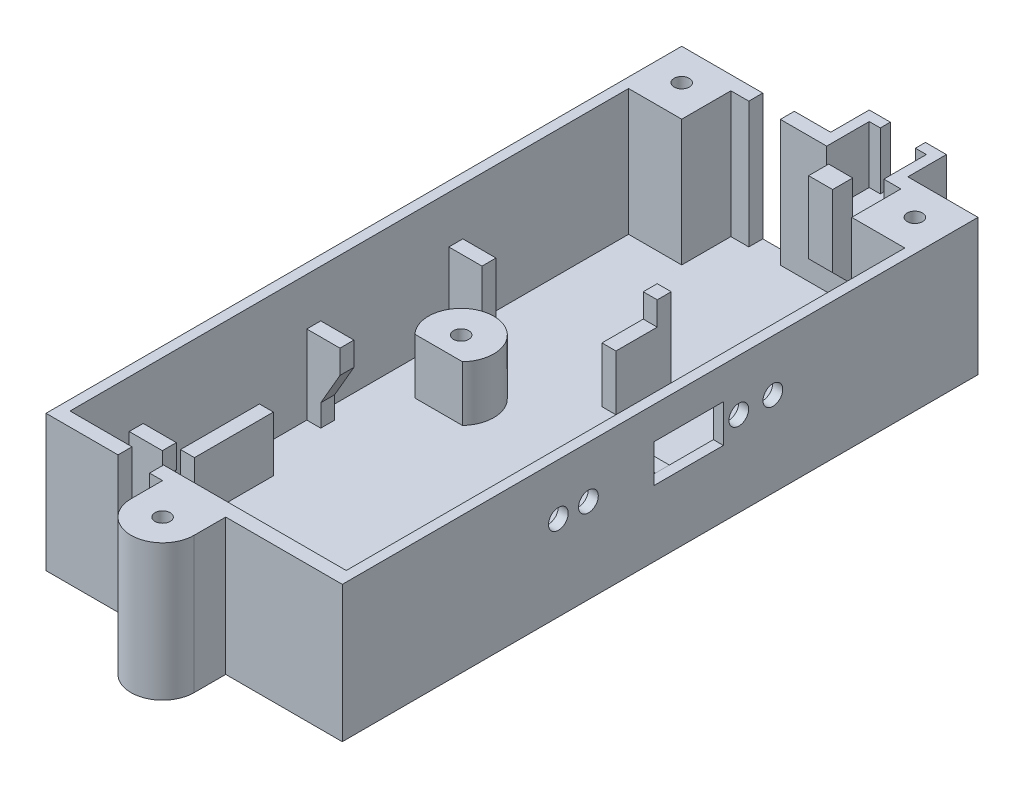
SolidWorks part; units mm, degrees
ref_plane "Front Plane" through (0, 0, 0) normal (0, 0, 1) x (1, 0, 0)
ref_plane "Top Plane" through (0, 0, 0) normal (0, 1, 0) x (1, 0, 0)
ref_plane "Right Plane" through (0, 0, 0) normal (1, 0, 0) x (0, 0, -1)
sketch "Sketch2" plane through (0, 0, 0) normal (0, 0, 1) x (1, 0, 0)
  line L0 (-30.2154, 3.088) -> (-30.2154, -12.912)
  line L1 (-30.2154, -12.912) -> (4.7846, -12.912)
  line L2 (4.7846, -12.912) -> (4.7846, 3.088)
  line L3 (-31.4854, 3.088) -> (-31.4854, -14.182)
  line L4 (-31.4854, -14.182) -> (6.0546, -14.182)
  line L5 (6.0546, -14.182) -> (6.0546, 3.088)
  line L6 (-31.4854, 3.088) -> (-30.2154, 3.088)
  line L7 (4.7846, 3.088) -> (6.0546, 3.088)
  dimension "D1" = 16
  dimension "D2" = 16
  dimension "D3" = 35
  dimension "D4" = 1.27
extrude "Boss-Extrude1" add sketch "Sketch2" along normal blind 77
sketch "Sketch3" plane through (0, 0, 77) normal (0, 0, 1) x (1, 0, 0)
  line L1 (-31.4854, 3.088) -> (6.0546, 3.088)
  line L2 (-31.4854, 3.088) -> (-31.4854, -14.182)
  line L3 (-31.4854, -14.182) -> (6.0546, -14.182)
  line L4 (6.0546, 3.088) -> (6.0546, -14.182)
extrude "Boss-Extrude2" add sketch "Sketch3" along normal blind 1.77
sketch "Sketch4" plane through (0, 0, 0) normal (0, 0, -1) x (-1, 0, 0)
  line L1 (-6.0546, 3.088) -> (31.4854, 3.088)
  line L2 (-6.0546, 3.088) -> (-6.0546, -14.182)
  line L3 (-6.0546, -14.182) -> (31.4854, -14.182)
  line L4 (31.4854, 3.088) -> (31.4854, -14.182)
extrude "Boss-Extrude3" add sketch "Sketch4" along normal blind 1.77
sketch "Sketch5" plane through (0, 0, -1.77) normal (0, 0, -1) x (-1, 0, 0)
  line L0 (31.4854, 3.088) -> (-6.0546, 3.088) construction
  line L1 (17.2154, 3.088) -> (21.2154, 3.088)
  line L2 (17.2154, 3.088) -> (17.2154, -12.912)
  line L3 (17.2154, -12.912) -> (21.2154, -12.912)
  line L4 (21.2154, 3.088) -> (21.2154, -12.912)
  line L5 (-4.7846, -12.912) -> (30.2154, -12.912) construction
  line L6 (30.2154, -12.912) -> (30.2154, 3.088) construction
  dimension "D1" = 4
  dimension "D2" = 9
extrude "Cut-Extrude2" cut sketch "Sketch5" against normal blind 1.77
sketch "Sketch6" plane through (0, 3.088, 0) normal (0, 1, 0) x (1, 0, 0)
  line L0 (4.7846, -77) -> (4.7846, 0) construction
  line L1 (-11.3454, 5.39) -> (-4.1054, 5.39)
  line L2 (-11.3454, 5.39) -> (-11.3454, -1.85)
  line L3 (-11.3454, -1.85) -> (-4.1054, -1.85)
  line L4 (-4.1054, 5.39) -> (-4.1054, -1.85)
  line L5 (-12.6154, 6.66) -> (-2.8354, 6.66)
  line L6 (-12.6154, 6.66) -> (-12.6154, -4.39)
  line L7 (-12.6154, -4.39) -> (-2.8354, -4.39)
  line L8 (-2.8354, 6.66) -> (-2.8354, -4.39)
  line L9 (-17.2154, 1.77) -> (6.0546, 1.77) construction
  dimension "D1" = 1.27
  dimension "D2" = 1.27
  dimension "D3" = 8.89
  dimension "D4" = 7.24
  dimension "D5" = 1.27
  dimension "D6" = 2.54
  dimension "D7" = 7.24
  dimension "D8" = 3.62
extrude "button_walls" add sketch "Sketch6" against normal blind 7.24
sketch "Sketch7" plane through (0, -4.152, 0) normal (0, -1, 0) x (1, 0, 0)
  line L1 (-12.6154, 4.39) -> (-2.8354, 4.39)
  line L2 (-12.6154, 4.39) -> (-12.6154, -6.66)
  line L3 (-12.6154, -6.66) -> (-2.8354, -6.66)
  line L4 (-2.8354, 4.39) -> (-2.8354, -6.66)
extrude "button_bottom" add sketch "Sketch7" along normal blind 1.27
sketch "Sketch8" plane through (0, 3.088, 0) normal (0, 1, 0) x (1, 0, 0)
  line L0 (-11.3454, 0) -> (-4.1054, 0) construction
  line L1 (-11.3454, 1.77) -> (-4.1054, 1.77)
  line L2 (-11.3454, 1.77) -> (-11.3454, 0)
  line L3 (-11.3454, 0) -> (-4.1054, 0)
  line L4 (-4.1054, 1.77) -> (-4.1054, 0)
extrude "button_cutout_middle" cut sketch "Sketch8" against normal blind 7.24
sketch "Sketch9" plane through (0, 3.088, 0) normal (0, 1, 0) x (1, 0, 0)
  line L0 (-7.7254, 9.378) -> (-7.7254, -7.9569) construction
  line L1 (-2.8354, 6.66) -> (-12.6154, 6.66) construction
  line L2 (-9.9454, 6.66) -> (-5.4954, 6.66)
  line L3 (-9.9454, 6.66) -> (-9.9454, 5.39)
  line L4 (-9.9454, 5.39) -> (-5.4954, 5.39)
  line L5 (-5.4954, 6.66) -> (-5.4954, 5.39)
  line L6 (-4.1054, 5.39) -> (-11.3454, 5.39) construction
  line L13 (-12.6154, -4.39) -> (-2.8354, -4.39) construction
  line L14 (-12.6154, 0) -> (-9.2454, 0)
  line L15 (-12.6154, 0) -> (-12.6154, -4.39)
  line L16 (-12.6154, -4.39) -> (-9.2454, -4.39)
  line L17 (-9.2454, 0) -> (-9.2454, -4.39)
  line L19 (-2.8354, 0) -> (-6.2054, 0)
  line L20 (-2.8354, 0) -> (-2.8354, -4.39)
  line L21 (-2.8354, -4.39) -> (-6.2054, -4.39)
  line L22 (-6.2054, 0) -> (-6.2054, -4.39)
  dimension "D1" = 4.45
  dimension "D2" = 2.22
  dimension "D3" = 1.52
  dimension "D4" = 1.52
extrude "button_cutout_front_back" cut sketch "Sketch9" against normal blind 7.24
sketch "Sketch10" plane through (0, -4.152, 0) normal (0, 1, 0) x (1, 0, 0)
  line L1 (-12.6154, 0) -> (-9.2454, 0)
  line L2 (-12.6154, 0) -> (-12.6154, -4.39)
  line L3 (-12.6154, -4.39) -> (-9.2454, -4.39)
  line L4 (-9.2454, 0) -> (-9.2454, -4.39)
  line L5 (-2.8354, 0) -> (-6.2054, 0)
  line L6 (-2.8354, 0) -> (-2.8354, -4.39)
  line L7 (-2.8354, -4.39) -> (-6.2054, -4.39)
  line L8 (-6.2054, 0) -> (-6.2054, -4.39)
extrude "button_cutout_bottom" cut sketch "Sketch10" against normal blind 1.27
chamfer "button_Chamfer1" distance 5 angle 45 1 edges at (-7.7254, -5.422, 0)
sketch "Sketch12" plane through (0, -12.912, 0) normal (0, 1, 0) x (1, 0, 0)
  line L0 (4.7846, -77) -> (-30.2154, -77) construction
  line L1 (-30.2154, -77) -> (4.7846, -77)
  line L2 (-30.2154, -77) -> (-30.2154, -75.23)
  line L3 (-30.2154, -75.23) -> (4.7846, -75.23)
  line L4 (4.7846, -77) -> (4.7846, -75.23)
  line L5 (4.7846, -77) -> (4.7846, 0) construction
  line L11 (4.7846, -77) -> (4.7846, 0) construction
  line L12 (-27.9854, -55.23) -> (-26.2154, -55.23)
  line L13 (-27.9854, -55.23) -> (-27.9854, -65.23)
  line L14 (-27.9854, -65.23) -> (-26.2154, -65.23)
  line L15 (-26.2154, -55.23) -> (-26.2154, -65.23)
  line L16 (4.7846, -37.73) -> (-60.4587, -37.73) construction
  line L17 (-2.7154, -35.96) -> (4.7846, -35.96)
  line L18 (-2.7154, -35.96) -> (-2.7154, -37.73)
  line L19 (-2.7154, -37.73) -> (4.7846, -37.73)
  line L20 (4.7846, -35.96) -> (4.7846, -37.73)
  line L21 (-25.7839, -37.73) -> (-19.7648, -37.73)
  line L22 (-54.4351, -21.6) -> (25.4799, -21.6) construction
  line L24 (-12.9854, -19.83) -> (-11.2154, -19.83)
  line L25 (-12.9854, -19.83) -> (-12.9854, -26.83)
  line L26 (-12.9854, -26.83) -> (-11.2154, -26.83)
  line L27 (-11.2154, -19.83) -> (-11.2154, -26.83)
  arc A0 (-19.7648, -37.73) -> (-25.7839, -37.73) centre (-22.7744, -34.8868) ccw
  circle A1 centre (-22.7744, -34.8868) radius 0.9652
  point P29 (-12.1004, -19.83)
  dimension "D11" = 8.2804
  dimension "D12" = 1.9304
  dimension "D1" = 1.77
  dimension "D2" = 31
  dimension "D3" = 1.77
  dimension "D4" = 10
  dimension "D5" = 10
  dimension "D6" = 1.77
  dimension "D7" = 7.5
  dimension "D8" = 37.5
  dimension "D9" = 42.1132
  dimension "D10" = 27.559
  dimension "D13" = 55.4
  dimension "D14" = 1.77
  dimension "D15" = 7
  dimension "D16" = 1.77
  dimension "D17" = 16
extrude "support_pcb_battery" add sketch "Sketch12" along normal blind 7
sketch "Sketch13" plane through (6.0546, 0, 0) normal (1, 0, 0) x (0, 0, -1)
  line L0 (-77, 3.088) -> (-77, -22.3902) construction
  line L1 (-81.5091, -5.912) -> (21.2567, -5.912) construction
  line L3 (-39.2868, -1.012) -> (-30.4868, -1.012)
  line L4 (-39.2868, -1.012) -> (-39.2868, -5.812)
  line L5 (-39.2868, -5.812) -> (-30.4868, -5.812)
  line L6 (-30.4868, -1.012) -> (-30.4868, -5.812)
  circle A0 centre (-51.3968, -3.412) radius 1.25
  circle A1 centre (-47.5868, -3.412) radius 1.25
  circle A2 centre (-24.2188, -3.412) radius 1.25
  point P10 (-30.4868, -3.412)
  point P11 (-34.8868, -1.012)
  dimension "D7" = 2.5
  dimension "D8" = 2.5
  dimension "D11" = 2.5
  dimension "D1" = 8.8
  dimension "D2" = 2.5
  dimension "D3" = 4.8
  dimension "D4" = 42.1132
  dimension "D5" = 2.5
  dimension "D6" = 2.5
  dimension "D9" = 25.6032
  dimension "D10" = 29.4132
  dimension "D12" = 2.5
  dimension "D13" = 52.7812
extrude "cutout_usb_3_leds" cut sketch "Sketch13" against normal blind 1.77
sketch "Sketch16" plane through (0, -5.912, 0) normal (0, 1, 0) x (1, 0, 0)
  line L0 (-11.2154, -26.83) -> (-11.2154, -19.83) construction
  line L1 (-12.9854, -19.83) -> (-11.2154, -19.83)
  line L2 (-12.9854, -19.83) -> (-12.9854, -21.6)
  line L3 (-12.9854, -21.6) -> (-11.2154, -21.6)
  line L4 (-11.2154, -19.83) -> (-11.2154, -21.6)
  dimension "D1" = 1.77
extrude "tab_pcb_retainer_len" add sketch "Sketch16" along normal blind 3
sketch "Sketch17" plane through (0, 3.088, 0) normal (0, 1, 0) x (1, 0, 0)
  line L0 (4.7846, -77) -> (-30.2154, -77) construction
  line L1 (-22.3614, -77) -> (-18.3614, -77)
  line L2 (-22.3614, -77) -> (-22.3614, -78.77)
  line L3 (-22.3614, -78.77) -> (-18.3614, -78.77)
  line L4 (-18.3614, -77) -> (-18.3614, -78.77)
  line L5 (6.0546, -78.77) -> (-31.4854, -78.77) construction
  line L7 (4.7846, -77) -> (4.7846, 0) construction
  point P8 (-20.3614, -77)
  dimension "D1" = 25.146
  dimension "D2" = 4
extrude "cutout_back_mot_wires" cut sketch "Sketch17" against normal up to surface (9 mm away) up to face at (-12.7154, -5.912, 76.115)
sketch "Sketch18" plane through (6.0546, 0, 0) normal (1, 0, 0) x (0, 0, -1)
  line L0 (-77, 3.088) -> (-77, -25.415) construction
  line L1 (-78.77, -5.912) -> (19.6061, -5.912) construction
  circle A0 centre (-28.5368, -3.412) radius 1.25
  dimension "D1" = 2.5
  dimension "D2" = 2.5
  dimension "D3" = 48.4632
extrude "cutout_chg_done_led" cut sketch "Sketch18" against normal blind 10
sketch "Sketch19" plane through (0, -12.912, 0) normal (0, 1, 0) x (1, 0, 0)
  line L0 (-30.2154, -77) -> (38.3127, -77) construction
  line L1 (4.7846, 0) -> (4.7846, -88.7648) construction
  line L2 (-26.0154, 10.814) -> (-26.0154, -88.7648) construction
  line L3 (-30.2154, -77) -> (-30.2154, 0) construction
  line L4 (-30.2154, -67.73) -> (-26.0154, -67.73)
  line L5 (-30.2154, -67.73) -> (-30.2154, -69.5)
  line L6 (-30.2154, -69.5) -> (-26.0154, -69.5)
  line L7 (-26.0154, -67.73) -> (-26.0154, -69.5)
  line L9 (-30.2154, -45.23) -> (-26.0154, -45.23)
  line L10 (-30.2154, -45.23) -> (-30.2154, -47)
  line L11 (-30.2154, -47) -> (-26.0154, -47)
  line L12 (-26.0154, -45.23) -> (-26.0154, -47)
  line L13 (-30.2154, -27.23) -> (-26.0154, -27.23)
  line L14 (-30.2154, -27.23) -> (-30.2154, -29)
  line L15 (-30.2154, -29) -> (-26.0154, -29)
  line L16 (-26.0154, -27.23) -> (-26.0154, -29)
  dimension "D1" = 30.8
  dimension "D2" = 1.77
  dimension "D3" = 7.5
  dimension "D4" = 1.77
  dimension "D5" = 30
  dimension "D6" = 1.77
  dimension "D7" = 48
extrude "tab_pcb_retainers_width" add sketch "Sketch19" along normal blind 10
sketch "Sketch20" plane through (0, 0, 69.5) normal (0, 0, 1) x (1, 0, 0)
  line L0 (-26.0154, -2.912) -> (-33.8352, -2.912) construction
  line L1 (-26.0154, -5.912) -> (-34.7157, -5.912) construction
  line L2 (-30.2154, -5.912) -> (-22.3614, -5.912) construction
  line L3 (-26.0154, -2.912) -> (-26.0154, -12.912) construction
  line L4 (-28.4454, -0.8533) -> (-28.4454, -17.345) construction
  line L5 (-30.2154, -5.912) -> (-30.2154, 3.088) construction
  line L9 (-26.0154, -12.912) -> (-26.0154, -5.912)
  line L15 (-26.0154, -5.912) -> (-28.4454, -10.1209)
  line L16 (-28.4454, -10.1209) -> (-28.4454, -12.912)
  line L17 (-28.4454, -12.912) -> (-26.0154, -12.912)
  dimension "D1" = 1.77
  dimension "D2" = 30
extrude "cutout_retainer_tab_1" cut sketch "Sketch20" against normal blind 1.77
sketch "Sketch21" plane through (0, 0, 47) normal (0, 0, 1) x (1, 0, 0)
  line L0 (-26.0154, -5.912) -> (-28.4454, -10.1209)
  line L1 (-28.4454, -10.1209) -> (-28.4454, -12.912)
  line L2 (-28.4454, -12.912) -> (-26.0154, -12.912)
  line L3 (-26.0154, -12.912) -> (-26.0154, -5.912)
extrude "cutout_retainer_tab_2" cut sketch "Sketch21" against normal blind 1.77
sketch "Sketch23" plane through (0, -14.182, 0) normal (0, -1, 0) x (1, 0, 0)
  line L0 (-12.7154, 88.9305) -> (-12.7154, -20.1968) construction
  line L1 (-37.0904, 86.77) -> (37.2604, 86.77) construction
  line L2 (-31.4854, 78.77) -> (6.0546, 78.77) construction
  line L3 (-37.0904, 82.77) -> (5.1204, 82.77) construction
  line L8 (6.0546, -1.77) -> (-1.9454, -1.77)
  line L9 (6.0546, -1.77) -> (6.0546, 6.23)
  line L10 (6.0546, 6.23) -> (-1.9454, 6.23)
  line L11 (-1.9454, -1.77) -> (-1.9454, 6.23)
  line L12 (-31.4854, -1.77) -> (-23.4854, -1.77)
  line L13 (-31.4854, -1.77) -> (-31.4854, 6.23)
  line L14 (-31.4854, 6.23) -> (-23.4854, 6.23)
  line L15 (-23.4854, -1.77) -> (-23.4854, 6.23)
  line L16 (-8.7154, 86.77) -> (-8.7154, 78.4197) construction
  line L18 (-16.7154, 88.4048) -> (-16.7154, 77.7225) construction
  line L20 (-16.7154, 82.77) -> (-16.7154, 78.77)
  line L21 (-16.7154, 78.77) -> (-8.7154, 78.77)
  line L22 (-8.7154, 78.77) -> (-8.7154, 82.77)
  arc A0 (-16.7154, 82.77) -> (-8.7154, 82.77) centre (-12.7154, 82.77) cw
  circle A2 centre (-27.4854, 2.23) radius 0.9652
  circle A3 centre (2.0546, 2.23) radius 0.9652
  circle A4 centre (-12.7154, 82.77) radius 0.9652
  point P21 (-12.7154, 82.77)
  point P23 (-12.7154, 86.77)
  point P24 (-12.7154, 86.77)
  point P25 (-16.7154, 82.77)
  point P26 (-16.7154, 78.77)
  point P31 (-8.7154, 78.77)
  point P32 (-8.7154, 82.77)
  line M18 (-31.4854, 78.77) -> (-31.4854, -1.77)
  line M19 (-31.4854, -1.77) -> (6.0546, -1.77)
  line M20 (6.0546, -1.77) -> (6.0546, 78.77)
  line M21 (6.0546, 78.77) -> (-31.4854, 78.77)
  dimension "D9" = 1.9304
  dimension "D14" = 1.9304
  dimension "D15" = 1.9304
  dimension "D1" = 8
  dimension "D2" = 8
  dimension "D3" = 8
  dimension "D4" = 8
  dimension "D5" = 8
  dimension "D6" = 4
  dimension "D7" = 4
  dimension "D8" = 4
  dimension "D10" = 4
  dimension "D11" = 4
  dimension "D12" = 4
  dimension "D13" = 4
extrude "casing_screw_posts" add sketch "Sketch23" along direction (0, -1, 0) on the side against the normal up to surface (17.27 mm away) contours A0 L20 L22 M21 | L15 L14 A2 M19 M18 | L11 L10 A3 M19 M20 region at (2.0546, -14.182, -1.6569) region at (-27.4854, -14.182, -1.6569) region at (-12.7154, -14.182, 78.8831) up to face at (-3.3264, 3.088, 23.6583)
